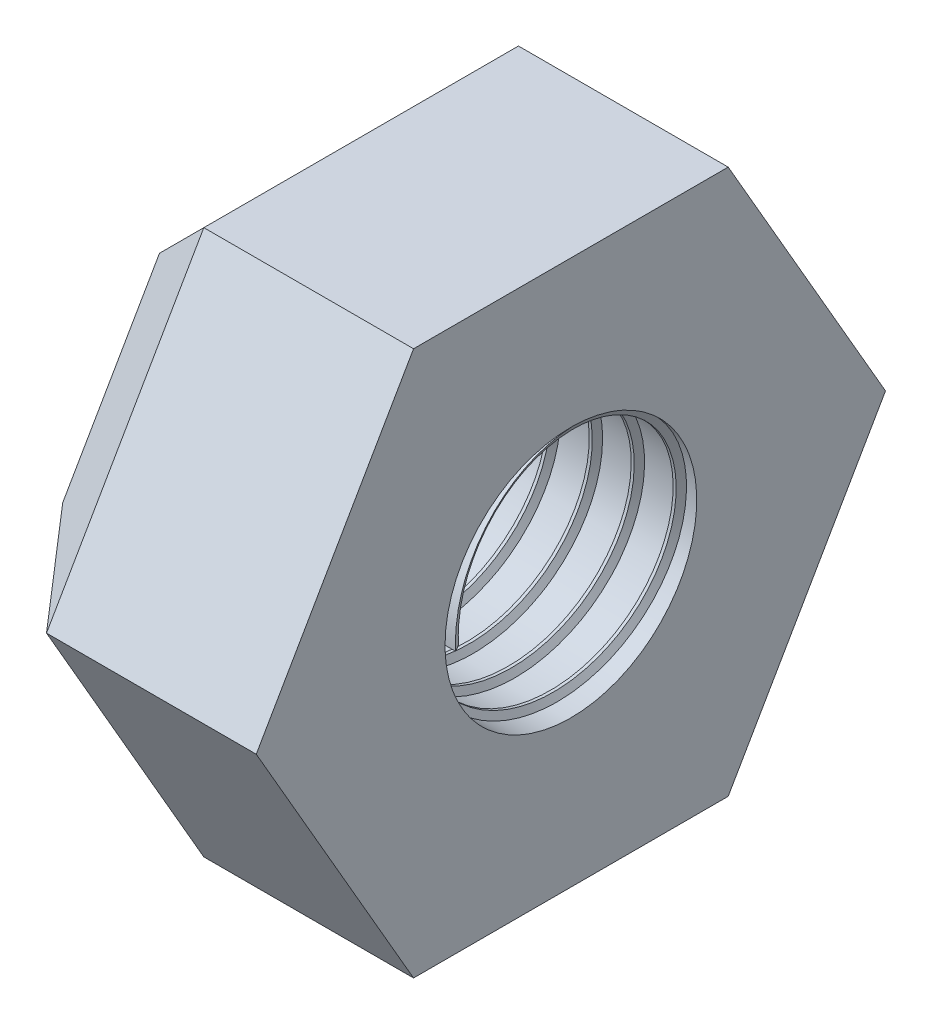
SolidWorks part; units mm, degrees
ref_plane "Front Plane" through (0, 0, 0) normal (0, 0, 1) x (1, 0, 0)
ref_plane "Top Plane" through (0, 0, 0) normal (0, 1, 0) x (1, 0, 0)
ref_plane "Right Plane" through (0, 0, 0) normal (1, 0, 0) x (0, 0, -1)
sketch "Sketch1" plane through (0, 0, 0) normal (1, 0, 0) x (0, 0, -1)
  line L1 (15, 0) -> (7.5, 12.9904)
  line L2 (7.5, 12.9904) -> (-7.5, 12.9904)
  line L3 (-7.5, 12.9904) -> (-15, 0)
  line L4 (-15, 0) -> (-7.5, -12.9904)
  line L5 (-7.5, -12.9904) -> (7.5, -12.9904)
  line L6 (7.5, -12.9904) -> (15, 0)
  circle A0 centre (0, 0) radius 12.9904 construction
  dimension "D1" = 15
extrude "Boss-Extrude1" add sketch "Sketch1" along normal blind 15
sketch "Sketch2" plane through (0, 0, 0) normal (-1, 0, 0) x (0, 0, 1)
  circle A0 centre (0, 0) radius 6
  dimension "D1" = 12
extrude "Cut-Extrude1" cut sketch "Sketch2" against normal blind 15
thread "Thread1" pitch 0.5773 method extrude profile "Thread Profile1" start angle 0, offset 0, length 15, pitch 2, diameter 12
ref_plane "Plane1" through (0, 0, -6) normal (0, -1, 0) x (0, 0, -1)
sketch "Thread Profile1" plane through (0, 0, -6) normal (0, -1, 0) x (0, 0, -1)
  line L0 (0, 0) -> (0, 0.5773) construction
  line L11 (0, 0) -> (0, 0.5051)
  line L12 (0, 0.5051) -> (-0.3125, 0.3247)
  line L13 (-0.3125, 0.3247) -> (-0.3125, 0.1804)
  line L15 (-0.3125, 0.1804) -> (0, 0)
  line L17 (-0.3125, 0.2526) -> (0, 0.2526) construction
  point P2 (0, 0)
  dimension "Pitch" = 0.5773
  dimension "Profile_Angle" = 60
  dimension "Profile_Land" = 0.1443
  dimension "Profile_Height" = 0.3125
chamfer "Chamfer1" distance 5 angle 45 6 edges at (0, 12.9904, 0) (0, 6.4952, -11.25) (0, -6.4952, -11.25) (0, -12.9904, 0) (0, -6.4952, 11.25) (0, 6.4952, 11.25)
